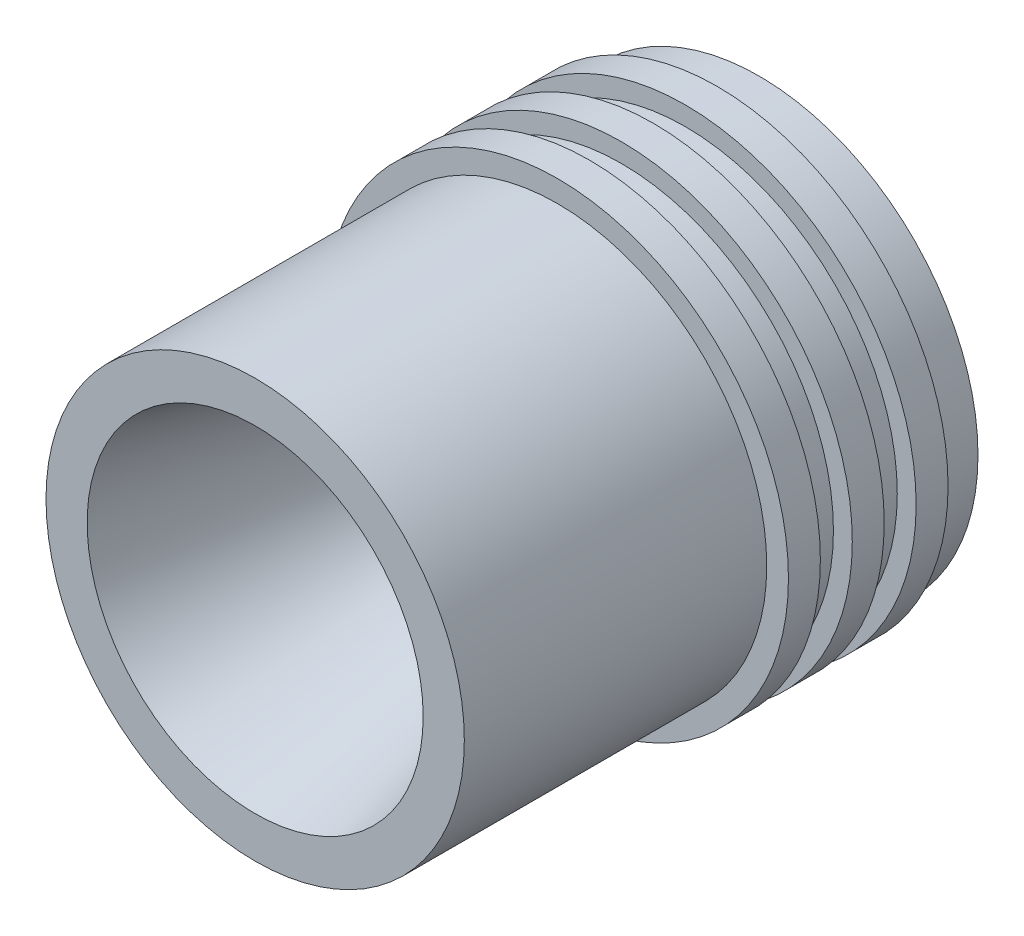
SolidWorks part; units mm, degrees
material "LE Phenolic"
ref_plane "Front Plane" through (0, 0, 0) normal (0, 0, 1) x (1, 0, 0)
ref_plane "Top Plane" through (0, 0, 0) normal (0, 1, 0) x (1, 0, 0)
ref_plane "Right Plane" through (0, 0, 0) normal (1, 0, 0) x (0, 0, -1)
sketch "Sketch1" plane through (0, 0, 0) normal (0, 1, 0) x (1, 0, 0)
  line L0 (69.8119, 139.7) -> (69.8119, 91.44)
  line L1 (63.246, 91.44) -> (63.246, 0)
  line L2 (63.246, 91.44) -> (69.8119, 91.44)
  line L8 (66.167, 139.7) -> (66.167, 152.4)
  line L10 (69.8119, 139.7) -> (66.167, 139.7)
  line L12 (66.167, 152.4) -> (59.817, 152.4)
  line L13 (59.817, 152.4) -> (18.415, 128.4965)
  line L14 (18.415, 128.4965) -> (18.415, 120.8765)
  line L15 (18.415, 120.8765) -> (50.8038, 0)
  line L16 (50.8038, 0) -> (63.246, 0)
  dimension "D1" = 69.8119
  dimension "D2" = 63.246
  dimension "D3" = 48.26
  dimension "D4" = 12.7
  dimension "D5" = 66.167
  dimension "D6" = 15
  dimension "D7" = 60
  dimension "D8" = 152.4
  dimension "D9" = 6.35
  dimension "D10" = 7.62
  dimension "D11" = 18.415
ref_axis "Axis1" through (0, 0, 8.1452) along (0, 0, -1)
revolve "Revolve1" add sketch "Sketch1" angle 360 about axis through (0, 0, 8.1452) along (0, 0, -1)
sketch "Sketch2" plane through (0, 0, 0) normal (0, 1, 0) x (1, 0, 0)
  line L0 (0, -8.1452) -> (0, 171.0497) construction
  line L1 (64.1096, 130.048) -> (70.4596, 130.048)
  line L2 (64.1096, 130.048) -> (64.1096, 120.396)
  line L3 (64.1096, 120.396) -> (70.4596, 120.396)
  line L4 (70.4596, 130.048) -> (70.4596, 120.396)
  line L5 (64.1096, 110.744) -> (70.4596, 110.744)
  line L6 (64.1096, 110.744) -> (64.1096, 101.092)
  line L7 (64.1096, 101.092) -> (70.4596, 101.092)
  line L8 (70.4596, 110.744) -> (70.4596, 101.092)
  line L9 (-69.8119, 91.44) -> (69.8119, 91.44) construction
  dimension "D1" = 9.652
  dimension "D2" = 9.652
  dimension "D3" = 64.1096
  dimension "D4" = 9.652
  dimension "D5" = 9.652
  dimension "D6" = 6.35
revolve "Cut-Revolve1" cut sketch "Sketch2" angle 360 about axis through (0, 0, 8.1452) along (0, 0, -1)
sketch "Sketch3" plane through (0, 0, 0) normal (0, 1, 0) x (1, 0, 0)
  line L0 (18.415, 120.8765) -> (50.8038, 0) construction
  line L1 (18.415, 128.4965) -> (18.415, 120.8765) construction
  line L2 (59.817, 152.4) -> (18.415, 128.4965) construction
  line L3 (18.415, 120.8765) -> (50.8038, 0) construction
  line L4 (18.415, 128.4965) -> (18.415, 120.8765) construction
  line L5 (59.817, 152.4) -> (18.415, 128.4965) construction
  line L6 (44.45, 143.5279) -> (44.45, 130.8279)
  line L7 (32.0875, 69.85) -> (18.415, 120.8765)
  line L8 (44.45, 130.8279) -> (39.1151, 69.85)
  line L9 (39.1151, 69.85) -> (32.0875, 69.85)
  line L10 (18.415, 120.8765) -> (18.415, 128.4965)
  line L11 (18.415, 128.4965) -> (44.45, 143.5279)
  line L12 (59.817, 152.4) -> (-59.817, 152.4) construction
  dimension "D1" = 12.7
  dimension "D2" = 44.45
  dimension "D3" = 5
  dimension "D4" = 82.55
revolve "Cut-Revolve2" cut sketch "Sketch3" angle 360 about axis through (0, 0, 8.1452) along (0, 0, -1)
ref_plane "Plane1" through (0, 0, -38.1) normal (0, 0, 1) x (1, 0, 0)
ref_plane "Plane2" through (0, 0, -76.2) normal (0, 0, 1) x (1, 0, 0)
ref_plane "Plane3" through (0, 0, -114.3) normal (0, 0, 1) x (1, 0, 0)
split "Split1" [suppressed] bodies to split 105
